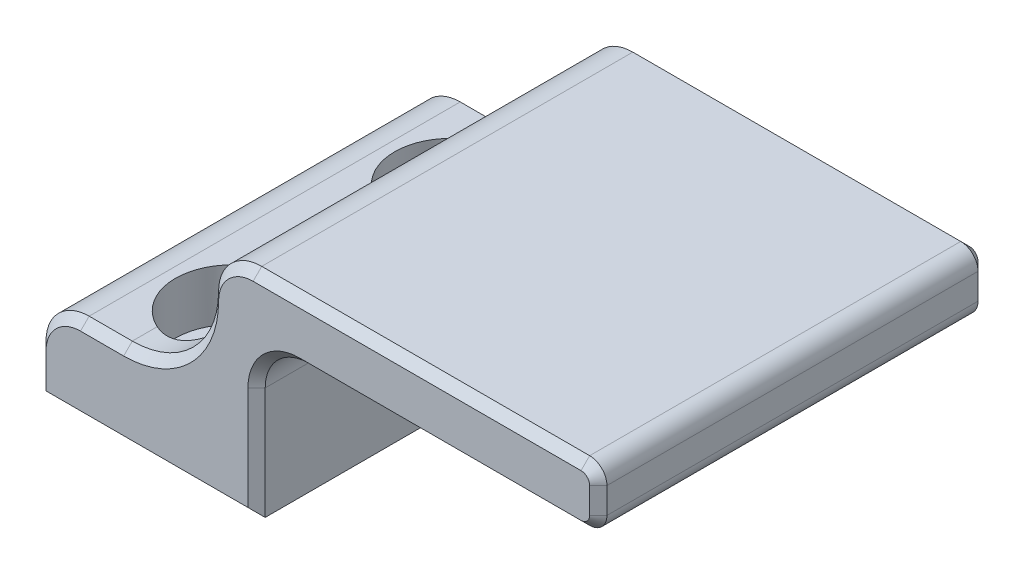
SolidWorks part; units mm, degrees
ref_plane "Front Plane" through (0, 0, 0) normal (0, 0, 1) x (1, 0, 0)
ref_plane "Top Plane" through (0, 0, 0) normal (0, 1, 0) x (1, 0, 0)
ref_plane "Right Plane" through (0, 0, 0) normal (1, 0, 0) x (0, 0, -1)
sketch "Sketch1" plane through (0, 0, 0) normal (0, 0, 1) x (1, 0, 0)
  line L0 (-22.7, -12.5) -> (2.7, -12.5)
  line L5 (2.7, -12.5) -> (2.7, 5.5)
  line L6 (2.7, 5.5) -> (42.3, 5.5)
  line L7 (42.3, 5.5) -> (42.3, 12.5)
  line L8 (42.3, 12.5) -> (-2.7, 12.5)
  line L9 (-2.7, 12.5) -> (-2.7, -2.5)
  line L10 (-2.7, -2.5) -> (-22.7, -2.5)
  line L11 (-22.7, -2.5) -> (-22.7, -12.5)
  line L12 (0, 12.5) -> (0, -12.5) construction
  line L13 (-2.7, 0) -> (2.7, 0) construction
  point P13 (0, 0)
  point P22 (0, 0)
  dimension "D1" = 18
  dimension "D2" = 45
  dimension "D3" = 25.4
  dimension "D4" = 20
  dimension "D5" = 10
  dimension "D6" = 7
extrude "Boss-Extrude1" add sketch "Sketch1" along normal mid plane 45
sketch "Sketch3" plane through (0, -2.5, 0) normal (0, 1, 0) x (1, 0, 0)
  line L2 (-22.7, -22.5) -> (2.7, -22.5) construction
  line L3 (-22.7, -22.5) -> (2.7, -22.5) construction
  circle A0 centre (-10, -12.7) radius 6.5
  circle A1 centre (-10, -12.7) radius 4
  point P3 (-10, -22.5)
  dimension "D1" = 13
  dimension "D2" = 8
  dimension "D3" = 12.7
extrude "Cut-Extrude1" cut sketch "Sketch3" against normal through all contours A1
extrude "Cut-Extrude2" cut sketch "Sketch3<4>" against normal blind 6
sketch "Sketch3<4>" plane through (0, -2.5, 0) normal (0, 1, 0) x (1, 0, 0) same geometry as "Sketch3"
mirror "Mirror1" about plane through (0, 0, 0) normal (0, 0, 1) of "Cut-Extrude2", "Cut-Extrude1"
sketch "Sketch9" plane through (0, 12.5, 0) normal (0, 1, 0) x (1, 0, 0)
  line L0 (25.9078, 11.1) -> (36.2078, -11.1) construction
  line L1 (42.3, -22.5) -> (42.3, 22.5) construction
  circle A0 centre (25.9078, 11.1) radius 1.0922
  circle A1 centre (36.2078, -11.1) radius 1.0922
  point P4 (31.0578, 0)
  dimension "D3" = 2.1844
  dimension "D1" = 22.2
  dimension "D2" = 10.3
  dimension "D4" = 5
extrude "Cut-Extrude3" [suppressed] cut sketch "Sketch9" against normal through all
fillet "Fillet1" radius 10 1 edges at (-2.7, -2.5, 0)
fillet "Fillet2" radius 5 3 edges at (2.7, 5.5, 0) (-22.7, -2.5, 0) (-2.7, 12.5, 0)
fillet "Fillet4" radius 2 2 edges at (42.3, 12.5, 0) (42.3, 5.5, 0)
chamfer "Chamfer1" distance 1 angle 45 26 edges at (42.3, 9, 22.5) (24, 5.5, 22.5) (4.1645, 4.0355, 22.5) (2.7, -6, 22.5) (-10, -12.5, 22.5) (-22.7, -10, 22.5) (-15.2, -2.5, 22.5) (-5.6289, 0.4289, 22.5) (21.3, 12.5, 22.5) (-15.2, -2.5, -22.5) (-22.7, -10, -22.5) (-10, -12.5, -22.5) (2.7, -6, -22.5) (4.1645, 4.0355, -22.5) (24, 5.5, -22.5) (42.3, 9, -22.5) (21.3, 12.5, -22.5) (-5.6289, 0.4289, -22.5) (41.7142, 6.0858, 22.5) (-21.2355, -3.9645, 22.5) (41.7142, 11.9142, 22.5) (-21.2355, -3.9645, -22.5) (41.7142, 6.0858, -22.5) (41.7142, 11.9142, -22.5) (-1.2355, 11.0355, 22.5) (-1.2355, 11.0355, -22.5)
